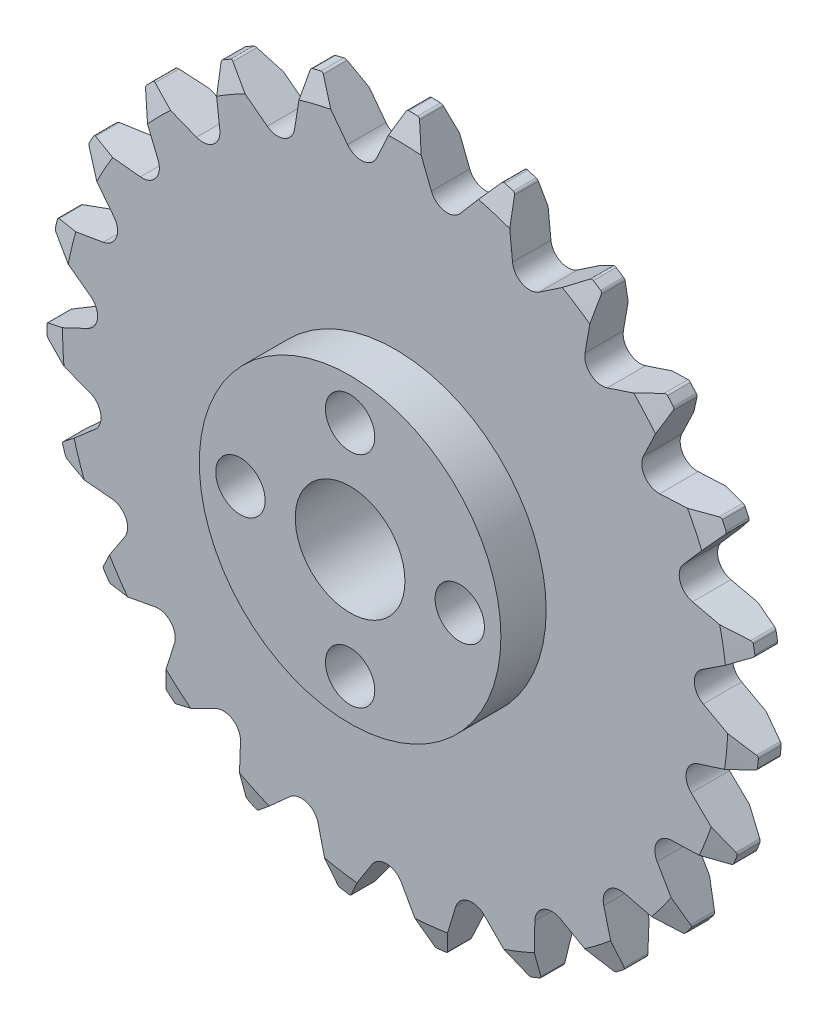
SolidWorks part; units mm, degrees
material "2024 Alloy"
ref_plane "Front Plane" through (0, 0, 0) normal (0, 0, 1) x (1, 0, 0)
ref_plane "Top Plane" through (0, 0, 0) normal (0, 1, 0) x (1, 0, 0)
ref_plane "Right Plane" through (0, 0, 0) normal (1, 0, 0) x (0, 0, -1)
sketch "Sketch1" plane through (0, 0, 0) normal (0, 1, 0) x (1, 0, 0)
  line L0 (26, 2.8) -> (0, 2.8)
  line L1 (0, 2.8) -> (0, 0)
  line L2 (0, 0) -> (26, 0)
  line L3 (26, 0) -> (26, 2.8)
  line L4 (0, 2.8) -> (0, 0) construction
revolve "Revolve1" add sketch "Sketch1" angle 360 about L4 reverse direction yes
sketch "Sketch2" plane through (0, 0, -2.8) normal (0, 0, -1) x (-1, 0, 0)
  line L0 (18.8013, 17.9586) -> (17.3085, 14.3114)
  line L1 (18.595, 12.5946) -> (22.5146, 13.0035)
  arc A0 (22.5146, 13.0035) -> (18.8013, 17.9586) centre (0, 0) ccw
  arc A1 (17.3085, 14.3114) -> (18.595, 12.5946) centre (18.4653, 13.8379) ccw
extrude "Cut-Extrude1" cut sketch "Sketch2" against normal through all
sketch "Sketch3" plane through (0, 0, -2.8) normal (0, 0, -1) x (-1, 0, 0)
  line L0 (22.9493, 12.2201) -> (20.5278, 9.1109)
  line L1 (21.3035, 7.1107) -> (25.188, 6.4469)
  arc A0 (25.188, 6.4469) -> (22.9493, 12.2201) centre (0, 0) ccw
  arc A1 (20.5278, 9.1109) -> (21.3035, 7.1107) centre (21.514, 8.3429) ccw
extrude "Cut-Extrude2" cut sketch "Sketch3" against normal through all
sketch "Sketch4" plane through (0, 0, -2.8) normal (0, 0, -1) x (-1, 0, 0)
  line L0 (25.3952, 5.5753) -> (22.2247, 3.2347)
  line L1 (22.4319, 1.0994) -> (25.9934, -0.5878)
  arc A0 (25.9934, -0.5878) -> (25.3952, 5.5753) centre (0, 0) ccw
  arc A1 (22.2247, 3.2347) -> (22.4319, 1.0994) centre (22.9671, 2.2291) ccw
extrude "Cut-Extrude3" cut sketch "Sketch4" against normal through all
sketch "Sketch5" plane through (0, 0, -2.8) normal (0, 0, -1) x (-1, 0, 0)
  line L0 (25.9577, -1.483) -> (22.2732, -2.8814)
  line L1 (21.8967, -4.9934) -> (24.8709, -7.5789)
  arc A0 (24.8709, -7.5789) -> (25.9577, -1.483) centre (0, 0) ccw
  arc A1 (22.2732, -2.8814) -> (21.8967, -4.9934) centre (22.7168, -4.05) ccw
extrude "Cut-Extrude4" cut sketch "Sketch5" against normal through all
sketch "Sketch6" plane through (0, 0, -2.8) normal (0, 0, -1) x (-1, 0, 0)
  line L0 (24.595, -8.4313) -> (20.6699, -8.7838)
  line L1 (19.7375, -10.7159) -> (21.9038, -14.0079)
  arc A0 (21.9038, -14.0079) -> (24.595, -8.4313) centre (0, 0) ccw
  arc A1 (20.6699, -8.7838) -> (19.7375, -10.7159) centre (20.7817, -10.0288) ccw
extrude "Cut-Extrude5" cut sketch "Sketch6" against normal through all
sketch "Sketch7" plane through (0, 0, -2.8) normal (0, 0, -1) x (-1, 0, 0)
  line L0 (21.4082, -14.7543) -> (17.5336, -14.0347)
  line L1 (16.1145, -15.6436) -> (17.3123, -19.3981)
  arc A0 (17.3123, -19.3981) -> (21.4082, -14.7543) centre (0, 0) ccw
  arc A1 (17.5336, -14.0347) -> (16.1145, -15.6436) centre (17.3053, -15.2637) ccw
extrude "Cut-Extrude6" cut sketch "Sketch7" against normal through all
sketch "Sketch8" plane through (0, 0, -2.8) normal (0, 0, -1) x (-1, 0, 0)
  line L0 (16.6337, -19.983) -> (13.0969, -18.2448)
  line L1 (11.2963, -19.4112) -> (11.4367, -23.3495)
  arc A0 (11.4367, -23.3495) -> (16.6337, -19.983) centre (0, 0) ccw
  arc A1 (13.0969, -18.2448) -> (11.2963, -19.4112) centre (12.5455, -19.3666) ccw
extrude "Cut-Extrude7" cut sketch "Sketch8" against normal through all
sketch "Sketch9" plane through (0, 0, -2.8) normal (0, 0, -1) x (-1, 0, 0)
  line L0 (10.6255, -23.7297) -> (7.6888, -21.1017)
  line L1 (5.6403, -21.7391) -> (4.713, -25.5693)
  arc A0 (4.713, -25.5693) -> (10.6255, -23.7297) centre (0, 0) ccw
  arc A1 (7.6888, -21.1017) -> (5.6403, -21.7391) centre (6.8552, -22.0332) ccw
extrude "Cut-Extrude8" cut sketch "Sketch9" against normal through all
sketch "Sketch10" plane through (0, 0, -2.8) normal (0, 0, -1) x (-1, 0, 0)
  line L0 (3.8293, -25.7165) -> (1.7105, -22.3936)
  line L1 (-0.4339, -22.4547) -> (-2.3603, -25.8926)
  arc A0 (-2.3603, -25.8926) -> (3.8293, -25.7165) centre (0, 0) ccw
  arc A1 (1.7105, -22.3936) -> (-0.4339, -22.4547) centre (0.6565, -23.0657) ccw
extrude "Cut-Extrude9" cut sketch "Sketch10" against normal through all
sketch "Sketch11" plane through (0, 0, -2.8) normal (0, 0, -1) x (-1, 0, 0)
  line L0 (-3.2509, -25.796) -> (-4.3946, -22.0247)
  line L1 (-6.476, -21.5049) -> (-9.2585, -24.2957)
  arc A0 (-9.2585, -24.2957) -> (-3.2509, -25.796) centre (0, 0) ccw
  arc A1 (-4.3946, -22.0247) -> (-6.476, -21.5049) centre (-5.5908, -22.3875) ccw
extrude "Cut-Extrude10" cut sketch "Sketch11" against normal through all
sketch "Sketch12" plane through (0, 0, -2.8) normal (0, 0, -1) x (-1, 0, 0)
  line L0 (-10.0901, -23.9623) -> (-10.1739, -20.0223)
  line L1 (-12.0379, -18.9602) -> (-15.4701, -20.8968)
  arc A0 (-15.4701, -20.8968) -> (-10.0901, -23.9623) centre (0, 0) ccw
  arc A1 (-10.1739, -20.0223) -> (-12.0379, -18.9602) centre (-11.4236, -20.0489) ccw
extrude "Cut-Extrude11" cut sketch "Sketch12" against normal through all
sketch "Sketch13" plane through (0, 0, -2.8) normal (0, 0, -1) x (-1, 0, 0)
  line L0 (-16.1808, -20.3514) -> (-15.1985, -16.5349)
  line L1 (-16.7069, -15.0093) -> (-20.5343, -15.9481)
  arc A0 (-20.5343, -15.9481) -> (-16.1808, -20.3514) centre (0, 0) ccw
  arc A1 (-15.1985, -16.5349) -> (-16.7069, -15.0093) centre (-16.4091, -16.2234) ccw
extrude "Cut-Extrude12" cut sketch "Sketch13" against normal through all
sketch "Sketch14" plane through (0, 0, -2.8) normal (0, 0, -1) x (-1, 0, 0)
  line L0 (-21.0716, -15.2312) -> (-19.096, -11.8213)
  line L1 (-20.1368, -9.9453) -> (-24.0756, -9.8167)
  arc A0 (-24.0756, -9.8167) -> (-21.0716, -15.2312) centre (0, 0) ccw
  arc A1 (-19.096, -11.8213) -> (-20.1368, -9.9453) centre (-20.1776, -11.1946) ccw
extrude "Cut-Extrude13" cut sketch "Sketch14" against normal through all
sketch "Sketch15" plane through (0, 0, -2.8) normal (0, 0, -1) x (-1, 0, 0)
  line L0 (-24.3995, -8.9813) -> (-21.5772, -6.2309)
  line L1 (-22.0733, -4.1437) -> (-25.8313, -2.9571)
  arc A0 (-25.8313, -2.9571) -> (-24.3995, -8.9813) centre (0, 0) ccw
  arc A1 (-21.5772, -6.2309) -> (-22.0733, -4.1437) centre (-22.4496, -5.3357) ccw
extrude "Cut-Extrude14" cut sketch "Sketch15" against normal through all
sketch "Sketch16" plane through (0, 0, -2.8) normal (0, 0, -1) x (-1, 0, 0)
  line L0 (-25.9178, -2.0654) -> (-22.4581, -0.1783)
  line L1 (-22.3727, 1.9653) -> (-25.6712, 4.1217)
  arc A0 (-25.6712, 4.1217) -> (-25.9178, -2.0654) centre (0, 0) ccw
  arc A1 (-22.4581, -0.1783) -> (-22.3727, 1.9653) centre (-23.0567, 0.919) ccw
extrude "Cut-Extrude15" cut sketch "Sketch16" against normal through all
sketch "Sketch17" plane through (0, 0, -2.8) normal (0, 0, -1) x (-1, 0, 0)
  line L0 (-25.514, 5.0037) -> (-21.6734, 5.8874)
  line L1 (-21.0128, 7.9285) -> (-23.6072, 10.8949)
  arc A0 (-23.6072, 10.8949) -> (-25.514, 5.0037) centre (0, 0) ccw
  arc A1 (-21.6734, 5.8874) -> (-21.0128, 7.9285) centre (-21.9537, 7.1056) ccw
extrude "Cut-Extrude16" cut sketch "Sketch17" against normal through all
sketch "Sketch18" plane through (0, 0, -2.8) normal (0, 0, -1) x (-1, 0, 0)
  line L0 (-23.2178, 11.7018) -> (-19.2813, 11.5165)
  line L1 (-18.0945, 13.3037) -> (-19.7924, 16.86)
  arc A0 (-19.7924, 16.86) -> (-23.2178, 11.7018) centre (0, 0) ccw
  arc A1 (-19.2813, 11.5165) -> (-18.0945, 13.3037) centre (-19.2226, 12.7651) ccw
extrude "Cut-Extrude17" cut sketch "Sketch18" against normal through all
sketch "Sketch19" plane through (0, 0, -2.8) normal (0, 0, -1) x (-1, 0, 0)
  line L0 (-19.1998, 17.5319) -> (-15.4592, 16.2915)
  line L1 (-13.8342, 17.6922) -> (-14.5097, 21.5748)
  arc A0 (-14.5097, 21.5748) -> (-19.1998, 17.5319) centre (0, 0) ccw
  arc A1 (-15.4592, 16.2915) -> (-13.8342, 17.6922) centre (-15.0657, 17.478) ccw
extrude "Cut-Extrude18" cut sketch "Sketch19" against normal through all
sketch "Sketch20" plane through (0, 0, -2.8) normal (0, 0, -1) x (-1, 0, 0)
  line L0 (-13.7577, 22.0618) -> (-10.4905, 19.8582)
  line L1 (-8.5479, 20.7685) -> (-8.1508, 24.6894)
  arc A0 (-8.1508, 24.6894) -> (-13.7577, 22.0618) centre (0, 0) ccw
  arc A1 (-10.4905, 19.8582) -> (-8.5479, 20.7685) centre (-9.7916, 20.8945) ccw
extrude "Cut-Extrude19" cut sketch "Sketch20" against normal through all
sketch "Sketch21" plane through (0, 0, -2.8) normal (0, 0, -1) x (-1, 0, 0)
  line L0 (-7.2953, 24.9555) -> (-4.7438, 21.9521)
  line L1 (-2.6277, 22.3046) -> (-1.1874, 25.9729)
  arc A0 (-1.1874, 25.9729) -> (-7.2953, 24.9555) centre (0, 0) ccw
  arc A1 (-4.7438, 21.9521) -> (-2.6277, 22.3046) centre (-3.7912, 22.7614) ccw
extrude "Cut-Extrude20" cut sketch "Sketch21" against normal through all
sketch "Sketch22" plane through (0, 0, -2.8) normal (0, 0, -1) x (-1, 0, 0)
  line L0 (-0.2919, 25.9984) -> (1.3547, 22.418)
  line L1 (3.4875, 22.1864) -> (5.864, 25.3301)
  arc A0 (5.864, 25.3301) -> (-0.2919, 25.9984) centre (0, 0) ccw
  arc A1 (1.3547, 22.418) -> (3.4875, 22.1864) centre (2.4903, 22.9402) ccw
extrude "Cut-Extrude21" cut sketch "Sketch22" against normal through all
sketch "Sketch23" plane through (0, 0, -2.8) normal (0, 0, -1) x (-1, 0, 0)
  line L0 (6.7332, 25.113) -> (7.3527, 21.2211)
  line L1 (9.344, 20.4228) -> (12.4805, 22.8087)
  arc A0 (12.4805, 22.8087) -> (6.7332, 25.113) centre (0, 0) ccw
  arc A1 (7.3527, 21.2211) -> (9.344, 20.4228) centre (8.5872, 21.4176) ccw
extrude "Cut-Extrude22" cut sketch "Sketch23" against normal through all
sketch "Sketch24" plane through (0, 0, -2.8) normal (0, 0, -1) x (-1, 0, 0)
  line L0 (13.2589, 22.3652) -> (12.8055, 18.4505)
  line L1 (14.5075, 17.1445) -> (18.1714, 18.5957)
  arc A0 (18.1714, 18.5957) -> (13.2589, 22.3652) centre (0, 0) ccw
  arc A1 (12.8055, 18.4505) -> (14.5075, 17.1445) centre (14.0472, 18.3066) ccw
extrude "Cut-Extrude23" cut sketch "Sketch24" against normal through all
sketch "Sketch25" plane through (0, 0, 0) normal (0, 1, 0) x (1, 0, 0)
  line L0 (11, 0) -> (0, 0)
  line L1 (0, 0) -> (0, -3.302)
  line L2 (0, -3.302) -> (11, -3.302)
  line L3 (11, -3.302) -> (11, 0)
  line L4 (0, 0) -> (0, -3.302) construction
revolve "Revolve2" add sketch "Sketch25" angle 360 about L4 reverse direction yes
hole_wizard "Ø8.0 (8) Diameter Hole1" positions "Sketch27" profile "Sketch26" hole size "Ø8.0" standard "ANSI Metric"
sketch "Sketch27" plane through (0, 0, 3.302) normal (0, 0, 1) x (1, 0, 0)
  point P0 (0, 0)
sketch "Sketch26" plane through (0, 0, 3.302) normal (1, 0, 0) x (0, -1, 0)
  line L0 (0, 0) -> (0, 6.102)
  line L1 (0, 6.102) -> (4, 6.102)
  line L2 (4, 6.102) -> (4, 0)
  line L5 (4, 0) -> (0, 0)
  line L11 (0, -6.35) -> (0, 107.95) construction
  dimension "Thru Hole Dia." = 8
  dimension "Thru Hole Depth" = 6.102
hole_wizard "Ø3.6 (3.6) Diameter Hole1" positions "Sketch29" profile "Sketch28" hole size "Ø3.6" standard "ANSI Metric"
sketch "Sketch29" plane through (0, 0, 3.302) normal (0, 0, 1) x (1, 0, 0)
  point P0 (0, 8)
  point P1 (-8, 0)
  point P2 (0, -8)
sketch "Sketch28" plane through (0, 8, 3.302) normal (1, 0, 0) x (0, -1, 0)
  line L0 (0, 0) -> (0, 6.102)
  line L1 (0, 6.102) -> (1.8, 6.102)
  line L2 (1.8, 6.102) -> (1.8, 0)
  line L5 (1.8, 0) -> (0, 0)
  line L11 (0, -6.35) -> (0, 107.95) construction
  dimension "Thru Hole Dia." = 3.6
  dimension "Thru Hole Depth" = 6.102
hole_wizard "Ø3.6 (3.6) Diameter Hole2" positions "Sketch31" profile "Sketch30" hole size "Ø3.6" standard "ANSI Metric"
sketch "Sketch31" plane through (0, 0, -2.8) normal (0, 0, -1) x (-1, 0, 0)
  point P0 (-8, 0)
sketch "Sketch30" plane through (8, 0, -2.8) normal (1, 0, 0) x (0, 1, 0)
  line L0 (0, 0) -> (0, 6.102)
  line L1 (0, 6.102) -> (1.8, 6.102)
  line L2 (1.8, 6.102) -> (1.8, 0)
  line L5 (1.8, 0) -> (0, 0)
  line L11 (0, -6.35) -> (0, 107.95) construction
  dimension "Thru Hole Dia." = 3.6
  dimension "Thru Hole Depth" = 6.102
fillet "Fillet1" radius 0.2 46 edges at (25.8313, -2.9571, -1.4) (25.9178, -2.0654, -1.4) (9.2585, -24.2957, -1.4) (10.0901, -23.9623, -1.4) (14.5097, 21.5748, -1.4) (13.7577, 22.0618, -1.4) (-13.2589, 22.3652, -1.4) (-12.4805, 22.8087, -1.4) (20.5343, -15.9481, -1.4) (21.0716, -15.2312, -1.4) (-18.8013, 17.9586, -1.4) (-18.1714, 18.5957, -1.4) (23.6072, 10.8949, -1.4) (23.2178, 11.7018, -1.4) (1.1874, 25.9729, -1.4) (0.2919, 25.9984, -1.4) (-22.9493, 12.2201, -1.4) (-22.5146, 13.0035, -1.4) (15.4701, -20.8968, -1.4) (16.1808, -20.3514, -1.4) (24.0756, -9.8167, -1.4) (24.3995, -8.9813, -1.4) (-25.3952, 5.5753, -1.4) (-25.188, 6.4469, -1.4) (25.6712, 4.1217, -1.4) (25.514, 5.0037, -1.4) (19.7924, 16.86, -1.4) (19.1998, 17.5319, -1.4) (-25.9577, -1.483, -1.4) (-25.9934, -0.5878, -1.4) (8.1508, 24.6894, -1.4) (7.2953, 24.9555, -1.4) (-5.864, 25.3301, -1.4) (-6.7332, 25.113, -1.4) (-24.595, -8.4313, -1.4) (-24.8709, -7.5789, -1.4) (-21.4082, -14.7543, -1.4) (-21.9038, -14.0079, -1.4) (-16.6337, -19.983, -1.4) (-17.3123, -19.3981, -1.4) (-10.6255, -23.7297, -1.4) (-11.4367, -23.3495, -1.4) (-3.8293, -25.7165, -1.4) (-4.713, -25.5693, -1.4) (3.2509, -25.796, -1.4) (2.3603, -25.8926, -1.4)
sketch "Sketch32" plane through (0, 0, 0) normal (1, 0, 0) x (0, 0, -1)
  line L0 (0, 24.2697) -> (0, 26.0477)
  line L1 (0, 26.0477) -> (0.5842, 26.0477)
  line L2 (0.5842, 26.0477) -> (0, 24.2697)
  line L3 (1.4, 25.8518) -> (1.4, 8.3868) construction
  line L4 (2.8, 25.8518) -> (0, 25.8518) construction
  line L5 (0, 0) -> (13.057, 0) construction
  line L6 (2.2158, 26.0477) -> (2.8, 24.2697)
  line L7 (2.8, 26.0477) -> (2.2158, 26.0477)
  line L8 (2.8, 24.2697) -> (2.8, 26.0477)
  dimension "D1" = 24.2697
  dimension "D2" = 1.778
  dimension "D3" = 0.5842
revolve "Cut-Revolve1" cut sketch "Sketch32" angle 360 about L5
